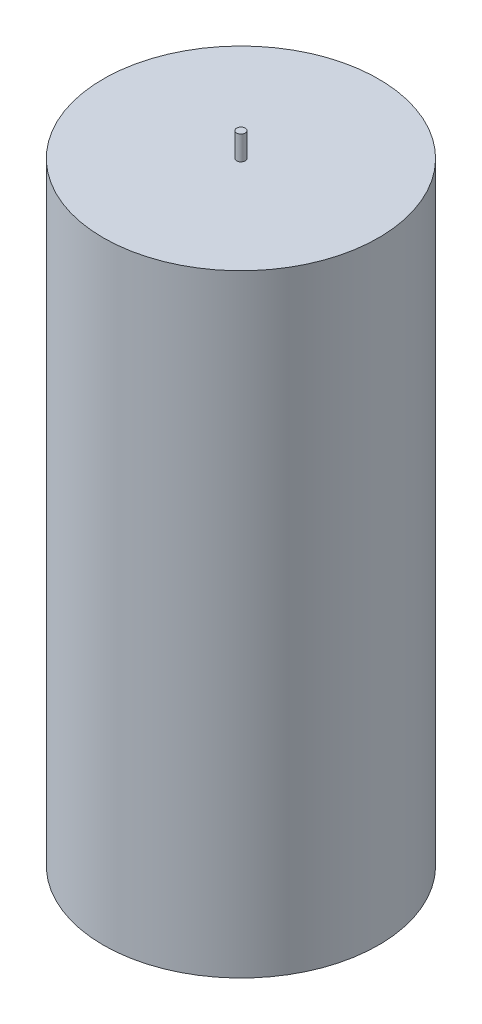
SolidWorks part; units mm, degrees
ref_plane "Alzado" through (0, 0, 0) normal (0, 0, 1) x (1, 0, 0)
ref_plane "Planta" through (0, 0, 0) normal (0, 1, 0) x (1, 0, 0)
ref_plane "Vista lateral" through (0, 0, 0) normal (1, 0, 0) x (0, 0, -1)
sketch "Croquis1" plane through (0, 0, 0) normal (0, 0, 1) x (1, 0, 0)
  line L0 (0, 192) -> (2.5, 192)
  line L1 (2.5, 192) -> (2.5, 178)
  line L2 (2.5, 178) -> (80, 178)
  line L3 (80, 178) -> (80, -178)
  line L4 (80, 0) -> (0, 0)
  line L5 (0, -192) -> (0, 192)
  line L6 (337.5089, 0) -> (-200.3399, 0) construction
  line L7 (0, 415.2531) -> (0, -321.1925) construction
  line L8 (2.5, -178) -> (80, -178)
  line L9 (2.5, -192) -> (2.5, -178)
  line L10 (0, -192) -> (2.5, -192)
  dimension "D1" = 80
  dimension "D2" = 2.5
  dimension "D3" = 178
  dimension "D4" = 192
revolve "Revolución1" add sketch "Croquis1" angle 360 about L7 region at (39.905, 89.2354, 0) region at (39.905, -89.2354, 0)
